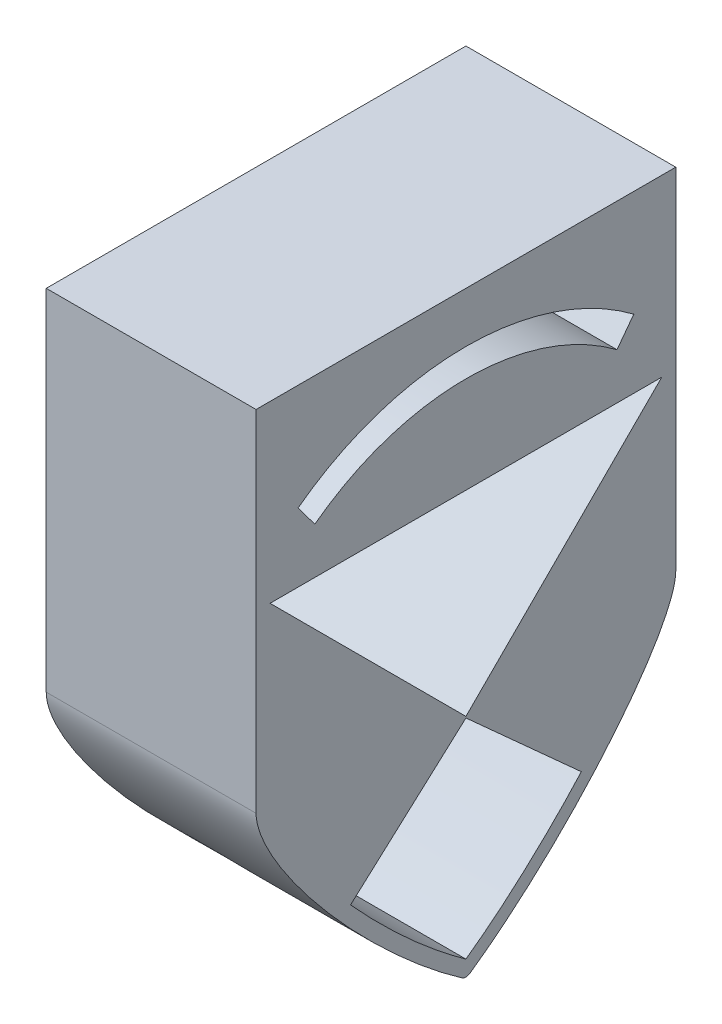
SolidWorks part; units mm, degrees
material "Commercially Pure CP-Ti UNS R50400 (SS)"
ref_plane "Front Plane" through (0, 0, 0) normal (0, 0, 1) x (1, 0, 0)
ref_plane "Top Plane" through (0, 0, 0) normal (0, 1, 0) x (1, 0, 0)
ref_plane "Right Plane" through (0, 0, 0) normal (1, 0, 0) x (0, 0, -1)
sketch "Sketch3" plane through (0, 0, 0) normal (1, 0, 0) x (0, 0, -1)
  line L1 (0, 0) -> (30, 0)
  line L2 (0, 0) -> (0, -45)
  line L3 (0, -45) -> (30, -45)
  line L4 (30, 0) -> (30, -45)
  dimension "D1" = 30
  dimension "D2" = 45
extrude "Boss-Extrude1" add sketch "Sketch3" along normal blind 15
fillet "Fillet1" radius 20 2 edges at (7.5, -45, -30) (7.5, -45, 0) conic radius 60
sketch "Sketch13" plane through (15, 0, 0) normal (1, 0, 0) x (0, 0, -1)
  line L0 (1, -12.5) -> (29, -12.5)
  line L1 (29, -12.5) -> (15, -26.5)
  line L2 (15, -26.5) -> (1, -12.5)
  line L3 (0, 0) -> (0, -25) construction
  line L4 (30, -25) -> (30, 0) construction
  point P7 (30, -12.5)
  point P9 (15, -12.5)
  dimension "D1" = 1
  dimension "D2" = 1
  dimension "D3" = 28
  dimension "D4" = 14
extrude "Cut-Extrude3" cut sketch "Sketch13" against normal through all
sketch "Sketch21" plane through (15, 0, 0) normal (1, 0, 0) x (0, 0, -1)
  line L0 (15, -26.5) -> (15, -26.6)
  line L1 (15, -26.6) -> (23.2483, -34.0481)
  line L2 (15, -26.6) -> (6.7517, -34.0481)
  spline S4 degree 3 poles (-1261.0101, -1573.2894) (96.0295, -111.269) (-3.097, -12.0314) (1.2569, -26.161) (1.4291, -26.5831) (1.7885, -27.3054) (1.9379, -27.5852) (2.1072, -27.882) (2.1267, -27.9161) (2.1302, -27.9222) (2.221, -28.08) (2.5229, -28.5896) (3.1139, -29.5019) (3.7159, -30.3413) (4.0573, -30.7953) (4.0965, -30.8473) (4.1051, -30.8586) (4.3419, -31.1717) (5.1155, -32.1666) (6.5528, -33.864) (7.8756, -35.2678) (8.7473, -36.1484) (8.9248, -36.3257) (9.6321, -37.0234) (10.8665, -38.197) (12.5527, -39.6586) (13.7056, -40.5658) (14.172, -40.9179) (14.1857, -40.9283) (14.2117, -40.9478) (14.2765, -40.9966) (72.602, -84.5888) (-125.8354, 318.5638) (-1474.5675, 1284.77) knots -2.397533 -2.397533 -2.397533 -2.397533 0.0625 0.0625 0.125 0.125 0.15625 0.15918 0.15918 0.160156 0.160156 0.1875 0.25 0.3125 0.318359 0.318359 0.320312 0.320312 0.375 0.5 0.625 0.625 0.65625 0.65625 0.75 0.875 0.957031 0.957031 0.958984 0.958984 0.960938 0.96875 9.785242 9.785242 9.785242 9.785242 only from (1, -25) to (14.9999, -41.5251)
  spline S5 degree 3 poles (1505.9367, 1283.3971) (156.7912, 317.1057) (-42.4154, -84.4487) (15.7371, -40.9863) (15.8151, -40.9275) (15.8542, -40.898) (15.8643, -40.8904) (16.318, -40.547) (17.4557, -39.651) (19.1248, -38.2045) (20.355, -37.0356) (21.06, -36.3406) (21.2374, -36.1637) (22.1141, -35.2785) (23.4445, -33.8673) (24.8896, -32.1605) (25.6672, -31.1598) (25.9052, -30.845) (25.913, -30.8346) (25.9523, -30.7826) (26.2933, -30.3287) (26.8947, -29.4892) (27.4853, -28.5764) (27.7871, -28.0663) (27.8777, -27.9083) (27.8805, -27.9035) (27.8999, -27.8696) (28.0681, -27.5742) (28.2165, -27.2957) (28.5736, -26.5767) (28.7448, -26.1565) (33.0825, -12.0468) (-65.969, -111.3392) (1293.5724, -1571.2605) knots -8.744692 -8.744692 -8.744692 -8.744692 0.03125 0.039062 0.042969 0.042969 0.044922 0.044922 0.125 0.25 0.34375 0.34375 0.375 0.375 0.5 0.625 0.679688 0.679688 0.681641 0.681641 0.6875 0.75 0.8125 0.839844 0.839844 0.84082 0.84082 0.84375 0.875 0.875 0.9375 0.9375 3.404672 3.404672 3.404672 3.404672 only from (14.9999, -41.5251) to (29, -25)
  spline S6 degree 3 poles (1, -25) (1, -25.1837) (1.0412, -25.4608) (1.2569, -26.161) (1.4291, -26.5831) (1.7885, -27.3054) (1.9379, -27.5852) (2.1072, -27.882) (2.1267, -27.9161) (2.1302, -27.9222) (2.221, -28.08) (2.5229, -28.5896) (3.1139, -29.5019) (3.7159, -30.3413) (4.0573, -30.7953) (4.0965, -30.8473) (4.1051, -30.8586) (4.3419, -31.1717) (5.1155, -32.1666) (6.5528, -33.864) (7.8756, -35.2678) (8.7473, -36.1484) (8.9248, -36.3257) (9.6321, -37.0234) (10.8665, -38.197) (12.5527, -39.6586) (13.7056, -40.5658) (14.172, -40.9179) (14.1857, -40.9283) (14.4713, -41.1434) (14.7384, -41.3391) (14.9999, -41.5251) knots 0 0 0 0 0.0625 0.0625 0.125 0.125 0.15625 0.15918 0.15918 0.160156 0.160156 0.1875 0.25 0.3125 0.318359 0.318359 0.320312 0.320312 0.375 0.5 0.625 0.625 0.65625 0.65625 0.75 0.875 0.957031 0.957031 0.958984 0.958984 1 1 1 1
  spline S7 degree 3 poles (14.9999, -41.5251) (15.2741, -41.33) (15.5546, -41.1243) (15.8542, -40.898) (15.8643, -40.8904) (16.318, -40.547) (17.4557, -39.651) (19.1248, -38.2045) (20.355, -37.0356) (21.06, -36.3406) (21.2374, -36.1637) (22.1141, -35.2785) (23.4445, -33.8673) (24.8896, -32.1605) (25.6672, -31.1598) (25.9052, -30.845) (25.913, -30.8346) (25.9523, -30.7826) (26.2933, -30.3287) (26.8947, -29.4892) (27.4853, -28.5764) (27.7871, -28.0663) (27.8777, -27.9083) (27.8805, -27.9035) (27.8999, -27.8696) (28.0681, -27.5742) (28.2165, -27.2957) (28.5736, -26.5767) (28.7448, -26.1565) (28.9591, -25.4593) (29, -25.1832) (29, -25) knots 0 0 0 0 0.042969 0.042969 0.044922 0.044922 0.125 0.25 0.34375 0.34375 0.375 0.375 0.5 0.625 0.679688 0.679688 0.681641 0.681641 0.6875 0.75 0.8125 0.839844 0.839844 0.84082 0.84082 0.84375 0.875 0.875 0.9375 0.9375 1 1 1 1
  dimension "D3" = 0.1
  dimension "D1" = 1
extrude "Cut-Extrude8" cut sketch "Sketch21" against normal through all contours S6 S7 L1 L2 region at (15, -34.192, -14.999)
sketch "Sketch23" plane through (15, 0, 0) normal (1, 0, 0) x (0, 0, -1)
  line L0 (30, 0) -> (0, 0) construction
  line L1 (30, -25) -> (30, 0) construction
  line L2 (0, 0) -> (0, -25) construction
  line L3 (27, -7.6) -> (25.8, -9.2)
  line L4 (4.2, -9.2) -> (3, -7.6)
  arc A0 (27, -7.6) -> (3, -7.6) centre (15, -23.6) ccw
  arc A1 (25.8, -9.2) -> (4.2, -9.2) centre (15, -23.6) ccw
  point P3 (15, -3.6)
  point P12 (15, 0)
  dimension "D1" = 20
  dimension "D2" = 3
  dimension "D3" = 3
  dimension "D4" = 3
  dimension "D5" = 3.6
  dimension "D6" = 2
extrude "Cut-Extrude9" cut sketch "Sketch23" against normal through all contours A1 L4 A0 L3
sketch "Sketch25" plane through (0, 0, -30) normal (0, 0, -1) x (-1, 0, 0)
  line L0 (0, -25) -> (0, 0) construction
  line L2 (-15, -25) -> (0, -25) construction
  circle A0 centre (-7.5, -25) radius 5
  dimension "D1" = 10
  dimension "D2" = 7.5
  dimension "D3" = 0
extrude "Cut-Extrude11" cut sketch "Sketch25" against normal blind 7 contours A0
fillet "Fillet2" radius 0.5 1 edges
